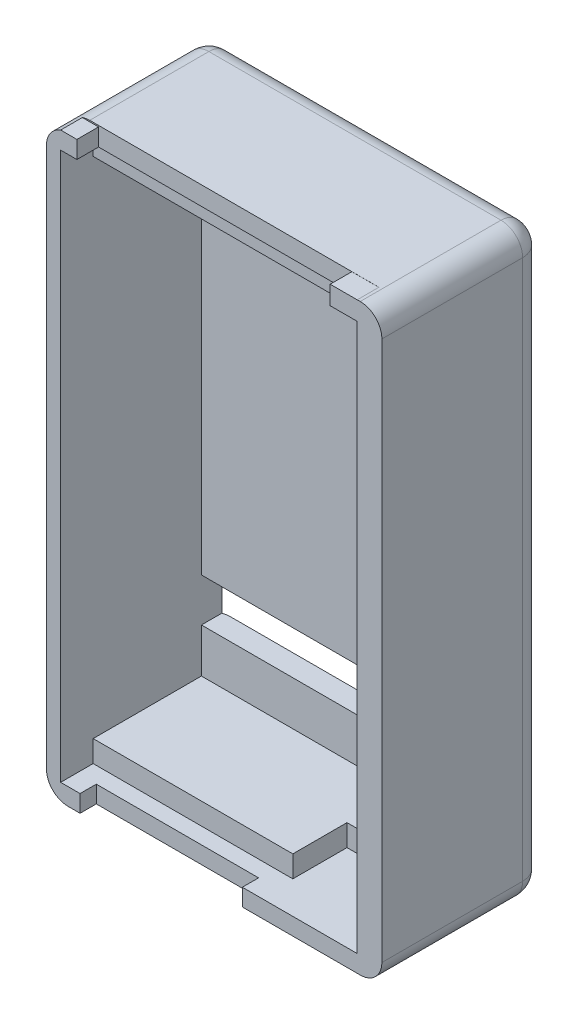
SolidWorks part; units mm, degrees
ref_plane "Front Plane" through (0, 0, 0) normal (0, 0, 1) x (1, 0, 0)
ref_plane "Top Plane" through (0, 0, 0) normal (0, 1, 0) x (1, 0, 0)
ref_plane "Right Plane" through (0, 0, 0) normal (1, 0, 0) x (0, 0, -1)
sketch "草图3" plane through (0, 0, 0) normal (0, 0, 1) x (1, 0, 0)
  line L6 (37.1016, -24.8877) -> (68.0762, -24.8877)
  line L7 (68.0762, -24.8877) -> (68.0762, -78.7564)
  line L10 (68.0762, -78.7564) -> (37.1016, -78.7564)
  line L11 (37.1016, -78.7564) -> (37.1016, -24.8877)
  line L12 (40.0889, -26.8877) -> (65.0889, -26.8877) construction
  line L13 (66.0762, -27.875) -> (66.0762, -75.875) construction
  line L14 (39.1016, -72.8424) -> (39.1016, -48.9006) construction
  line L16 (39.1016, -29.6037) -> (39.1016, -27.875) construction
  line L17 (39.1016, -48.9006) -> (39.1016, -29.6496) construction
  line L18 (39.1016, -75.875) -> (39.1016, -72.8424) construction
  line L19 (58.7612, -76.8631) -> (40.0889, -76.8624) construction
  line L20 (58.7612, -75.262) -> (58.7612, -76.8631) construction
  line L21 (62.9649, -75.2493) -> (58.7739, -75.2493) construction
  line L22 (62.9776, -76.8751) -> (62.9776, -75.262) construction
  line L23 (65.0889, -76.8624) -> (62.9776, -76.9001) construction
  line L24 (39.1016, -29.6037) -> (39.1016, -27.875)
  line L25 (39.1016, -48.9006) -> (39.1016, -29.6496)
  line L26 (39.1016, -72.8424) -> (39.1016, -48.9006)
  line L27 (39.1016, -75.875) -> (39.1016, -72.8424)
  line L28 (58.7612, -76.8631) -> (40.0889, -76.8624)
  line L29 (58.7612, -75.262) -> (58.7612, -76.8631)
  line L30 (62.9649, -75.2493) -> (58.7739, -75.2493)
  line L31 (62.9776, -76.8751) -> (62.9776, -75.262)
  line L32 (65.0889, -76.8624) -> (62.9776, -76.9001)
  line L33 (66.0762, -27.875) -> (66.0762, -75.875)
  line L34 (40.0889, -26.8877) -> (65.0889, -26.8877)
  arc A0 (39.1016, -75.875) -> (40.0889, -76.8624) centre (40.0889, -75.875) ccw construction
  arc A1 (65.0889, -76.8624) -> (66.0762, -75.875) centre (65.0889, -75.875) ccw construction
  arc A2 (66.0762, -27.875) -> (65.0889, -26.8877) centre (65.0889, -27.875) ccw construction
  arc A3 (40.0889, -26.8877) -> (39.1016, -27.875) centre (40.0889, -27.875) ccw construction
  arc A4 (39.1016, -75.875) -> (40.0889, -76.8624) centre (40.0889, -75.875) ccw
  arc A5 (65.0889, -76.8624) -> (66.0762, -75.875) centre (65.0889, -75.875) ccw
  arc A6 (66.0762, -27.875) -> (65.0889, -26.8877) centre (65.0889, -27.875) ccw
  arc A7 (40.0889, -26.8877) -> (39.1016, -27.875) centre (40.0889, -27.875) ccw
  dimension "D1" = 2
  dimension "D2" = 2
  dimension "D3" = 2
extrude "凸台-拉伸1" add sketch "草图3" along normal blind 15 contours L11 L10 L7 L6 region at (52.5889, -51.822, 0)
sketch "草图5" plane through (0, 0, 15) normal (0, 0, 1) x (1, 0, 0)
  line L1 (38.4139, -26.6161) -> (65.7955, -26.6161)
  line L2 (65.7955, -26.6161) -> (65.7955, -77.1753)
  line L3 (65.7955, -77.1753) -> (38.4139, -77.1753)
  line L4 (38.4139, -77.1753) -> (38.4139, -26.6161)
extrude "切除-拉伸1" cut sketch "草图5" against normal blind 13
sketch "草图6" plane through (0, 0, 2) normal (0, 0, 1) x (1, 0, 0)
  line L0 (38.4139, -26.6161) -> (38.4139, -77.1753) construction
  line L1 (38.4139, -26.6161) -> (65.7955, -26.6161)
  line L2 (38.4139, -26.6161) -> (38.4139, -28.6161)
  line L3 (38.4139, -28.6161) -> (65.7955, -28.6161)
  line L4 (65.7955, -26.6161) -> (65.7955, -28.6161)
  line L5 (65.7955, -26.6161) -> (38.4139, -26.6161) construction
  line L6 (65.7955, -77.1753) -> (65.7955, -26.6161) construction
  line L7 (65.7955, -77.1753) -> (65.7955, -26.6161) construction
  line L8 (38.4139, -77.1753) -> (65.7955, -77.1753)
  line L9 (38.4139, -77.1753) -> (38.4139, -75.1753)
  line L10 (38.4139, -75.1753) -> (65.7955, -75.1753)
  line L11 (65.7955, -77.1753) -> (65.7955, -75.1753)
extrude "凸台-拉伸2" add sketch "草图6" along normal blind 10
sketch "草图9" plane through (0, 0, 15) normal (0, 0, 1) x (1, 0, 0)
  line L0 (37.1016, -24.8877) -> (68.0762, -24.8877) construction
  line L1 (38.4139, -26.6161) -> (65.8048, -26.6161)
  line L2 (38.4139, -26.6161) -> (38.4139, -24.8877)
  line L3 (38.4139, -24.8877) -> (65.8048, -24.8877)
  line L4 (65.8048, -26.6161) -> (65.8048, -24.8877)
extrude "切除-拉伸3" cut sketch "草图9" against normal blind 2
fillet "圆角1" radius 2 4 edges at (68.0762, -78.7564, 7.5) (37.1016, -78.7564, 7.5) (37.1016, -24.8877, 7.5) (68.0762, -24.8877, 7.5)
sketch "草图11" plane through (0, 0, 2) normal (0, 0, 1) x (1, 0, 0)
  line L0 (38.4139, -28.6161) -> (38.4139, -75.1753) construction
  line L1 (38.4139, -32.8271) -> (65.7955, -32.8271)
  line L2 (38.4139, -32.8271) -> (38.4139, -36.8271)
  line L3 (38.4139, -36.8271) -> (65.7955, -36.8271)
  line L4 (65.7955, -32.8271) -> (65.7955, -36.8271)
  line L5 (65.7955, -77.1753) -> (65.7955, -26.6161) construction
  line L7 (38.4139, -67.0903) -> (65.7955, -67.0903)
  line L8 (38.4139, -67.0903) -> (38.4139, -71.0903)
  line L9 (38.4139, -71.0903) -> (65.7955, -71.0903)
  line L10 (65.7955, -67.0903) -> (65.7955, -71.0903)
extrude "切除-拉伸4" cut sketch "草图11" against normal blind 10
sketch "草图12" plane through (0, 0, 12) normal (0, 0, 1) x (1, 0, 0)
  line L0 (65.7955, -75.1753) -> (38.4139, -75.1753) construction
  line L1 (56.855, -75.1753) -> (62.9048, -75.1753)
  line L2 (56.855, -75.1753) -> (56.855, -77.1753)
  line L3 (56.855, -77.1753) -> (62.9048, -77.1753)
  line L4 (62.9048, -75.1753) -> (62.9048, -77.1753)
  line L5 (38.4139, -77.1753) -> (65.7955, -77.1753) construction
extrude "切除-拉伸5" cut sketch "草图12" against normal blind 5
sketch "草图14" plane through (0, 0, 13) normal (0, 0, 1) x (1, 0, 0)
  line L0 (38.4139, -26.6161) -> (65.7955, -26.6161) construction
  line L1 (38.4139, -25.0096) -> (39.9139, -25.0096)
  line L2 (38.4139, -25.0096) -> (38.4139, -26.6161)
  line L3 (38.4139, -26.6161) -> (39.9139, -26.6161)
  line L4 (39.9139, -25.0096) -> (39.9139, -26.6161)
  line L6 (65.8048, -24.8943) -> (63.3048, -24.8943)
  line L7 (65.8048, -24.8943) -> (65.8048, -26.6161)
  line L8 (65.8048, -26.6161) -> (63.3048, -26.6161)
  line L9 (63.3048, -24.8943) -> (63.3048, -26.6161)
  point P11 (0, 0)
extrude "凸台-拉伸3" add sketch "草图14" along normal up to surface (2 mm away) contours L2 L1 L4 L3 | L7 L6 L9 L8 up to face at (55.5197, -49.7982, 15)
sketch "草图17" plane through (0, 0, 15) normal (0, 0, 1) x (1, 0, 0)
  line L1 (40.2057, -77.1564) -> (55.1901, -77.1564)
  line L2 (40.2057, -77.1564) -> (40.2057, -78.7564)
  line L3 (40.2057, -78.7564) -> (55.1901, -78.7564)
  line L4 (55.1901, -77.1564) -> (55.1901, -78.7564)
extrude "切除-拉伸8" cut sketch "草图17" against normal blind 1.5
fillet "圆角2" radius 2 8 edges at (37.6874, -25.4734, 0) (37.1016, -51.822, 0) (37.6874, -78.1706, 0) (52.5889, -78.7564, 0) (67.4904, -78.1706, 0) (68.0762, -51.822, 0) (67.4904, -25.4734, 0) (52.5889, -24.8877, 0)
